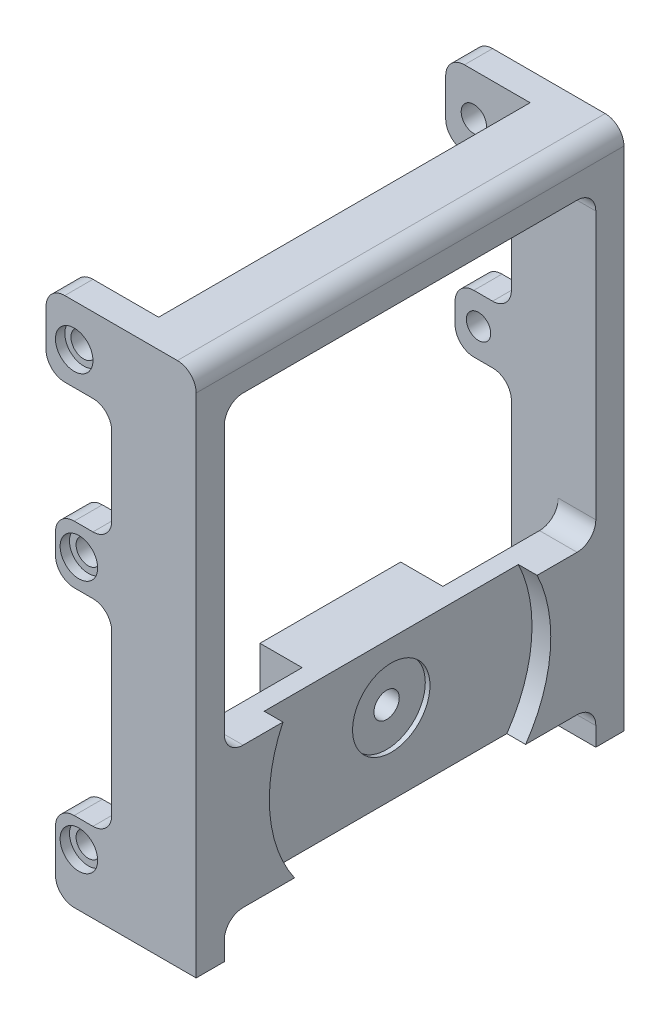
SolidWorks part; units mm, degrees
material "Esun Hard Tough Resin"
ref_plane "Front Plane" through (0, 0, 0) normal (0, 0, 1) x (1, 0, 0)
ref_plane "Top Plane" through (0, 0, 0) normal (0, 1, 0) x (1, 0, 0)
ref_plane "Right Plane" through (0, 0, 0) normal (1, 0, 0) x (0, 0, -1)
sketch "Sketch1" plane through (0, 0, 0) normal (0, 0, 1) x (1, 0, 0)
  line L0 (0, 48) -> (6, 48)
  line L1 (0, 0) -> (15, 0)
  line L2 (0, 0) -> (0, 8.5)
  line L3 (0, 56) -> (15, 56)
  line L4 (15, 0) -> (15, 56)
  line L5 (6, 48) -> (6, 35.68)
  line L6 (6, 35.68) -> (0, 35.68)
  line L7 (0, 29.52) -> (6, 29.52)
  line L8 (6, 29.52) -> (6, 8.5)
  line L9 (6, 8.5) -> (0, 8.5)
  line L10 (0, 48) -> (0, 56)
  line L11 (0, 29.52) -> (0, 35.68)
  dimension "D1" = 56
  dimension "D2" = 15
  dimension "D3" = 8.5
  dimension "D4" = 8
  dimension "D5" = 12.32
  dimension "D6" = 6.16
  dimension "D7" = 6
  dimension "D8" = 6
extrude "Boss-Extrude1" add sketch "Sketch1" along normal blind 3
sketch "Sketch2" plane through (0, 0, 3) normal (0, 0, 1) x (1, 0, 0)
  line L0 (6, 48) -> (6, 35.68) construction
  line L1 (6, 29.52) -> (6, 8.5) construction
  line L2 (0, 0) -> (15, 0) construction
  circle A0 centre (2, 51.5) radius 1.35
  circle A1 centre (2.5, 5.6) radius 1.3
  circle A2 centre (2.5, 32.6) radius 1.3
  dimension "D1" = 2.7
  dimension "D4" = 2.6
  dimension "D6" = 2.6
  dimension "D2" = 4
  dimension "D3" = 3.5
  dimension "D5" = 5.6
  dimension "D7" = 3.5
  dimension "D8" = 27
  dimension "D9" = 18.9
extrude "Cut-Extrude1" cut sketch "Sketch2" against normal through all
sketch "Sketch3" plane through (0, 0, 3) normal (0, 0, 1) x (1, 0, 0)
  line L1 (15, 56) -> (8, 56)
  line L2 (15, 56) -> (15, 51.5)
  line L3 (15, 51.5) -> (8, 51.5)
  line L4 (8, 56) -> (8, 51.5)
  dimension "D1" = 4.5
  dimension "D2" = 7
extrude "Boss-Extrude2" add sketch "Sketch3" along normal blind 19.8
sketch "Sketch4" plane through (0, 0, 3) normal (0, 0, 1) x (1, 0, 0)
  line L0 (15, 0) -> (15, 51.5) construction
  line L1 (15, 4) -> (11, 4)
  line L2 (15, 4) -> (15, 19)
  line L3 (15, 19) -> (11, 19)
  line L4 (11, 4) -> (11, 19)
  line L5 (0, 0) -> (15, 0) construction
  dimension "D1" = 4
  dimension "D2" = 15
  dimension "D3" = 4
extrude "Boss-Extrude3" add sketch "Sketch4" along normal blind 19.8
sketch "Sketch5" plane through (15, 0, 0) normal (1, 0, 0) x (0, 0, -1)
  line L0 (-22.8, 4) -> (-22.8, 19) construction
  line L2 (-3, 0) -> (0, 0) construction
  line L3 (-22.8, 19) -> (-22.8, -2.44)
  circle A0 centre (-22.8, 12.56) radius 15
  line M7 (-3, 19) -> (-22.8, 19)
  line M8 (-22.8, 19) -> (-22.8, 4)
  dimension "D2" = 30
  dimension "D1" = 12.56
extrude "Cut-Extrude2" cut sketch "Sketch5" against normal blind 2 contours A0 M8 M7 region at (15, 9.4935, 16.1213)
sketch "Sketch7" plane through (13, 0, 0) normal (1, 0, 0) x (0, 0, -1)
  circle A0 centre (-22.8, 12.56) radius 4.125
  dimension "D1" = 8.25
extrude "Cut-Extrude3" cut sketch "Sketch7" against normal blind 0.5
sketch "Sketch9" plane through (11, 0, 0) normal (-1, 0, 0) x (0, 0, 1)
  line L0 (22.8, 4) -> (3, 4) construction
  line L1 (22.8, 19) -> (15.3, 19)
  line L2 (22.8, 19) -> (22.8, 4)
  line L3 (22.8, 4) -> (15.3, 4)
  line L4 (15.3, 19) -> (15.3, 4)
  dimension "D1" = 7.5
extrude "Boss-Extrude4" add sketch "Sketch9" along normal blind 4.5
sketch "Sketch12" plane through (12.5, 0, 0) normal (1, 0, 0) x (0, 0, -1)
  line L0 (-22.8, 8.435) -> (-22.8, 16.685) construction
  line L1 (-3, 0) -> (0, 0) construction
  circle A0 centre (-22.8, 12.56) radius 1.35
  dimension "D1" = 2.7
  dimension "D2" = 12.56
extrude "Cut-Extrude4" cut sketch "Sketch12" against normal through all
sketch "Sketch13" plane through (0, 0, 0) normal (-1, 0, 0) x (0, 0, 1)
  line L4 (0, 56) -> (0, 48)
  line L5 (0, 48) -> (3, 48)
  line L6 (3, 48) -> (3, 56)
  line L7 (3, 56) -> (0, 56)
  line L8 (0, 56) -> (0, 48)
  line L9 (0, 48) -> (3, 48)
  line L10 (3, 48) -> (3, 56)
  line L11 (3, 56) -> (0, 56)
  dimension "D1" = 0
extrude "Boss-Extrude5" add sketch "Sketch13" along normal blind 1
fillet "Fillet1" radius 2 14 edges at (0, 8.5, 1.5) (6, 8.5, 1.5) (6, 29.52, 1.5) (0, 29.52, 1.5) (6, 35.68, 1.5) (0, 35.68, 1.5) (6, 48, 1.5) (15, 56, 11.4) (0, 0, 1.5) (-1, 56, 1.5) (-1, 48, 1.5) (11.5, 51.5, 3) (13, 4, 3) (13, 19, 3)
mirror "Mirror1" about plane through (0, 0, 22.8) normal (0, 0, 1) of bodies 110 104
sketch "Sketch14" plane through (0, 0, 0) normal (0, 0, -1) x (-1, 0, 0)
  circle A0 centre (-2, 51.5) radius 2
  circle A1 centre (-2.5, 32.6) radius 2
  circle A2 centre (-2.5, 5.6) radius 2
  dimension "D1" = 4
extrude "Cut-Extrude5" cut sketch "Sketch14" against normal blind 1
ref_plane "Plane1" through (0, 0, 22.8) normal (0, 0, -1) x (-1, 0, 0)
mirror "Mirror2" about plane through (0, 0, 22.8) normal (0, 0, -1) of "Cut-Extrude5"
